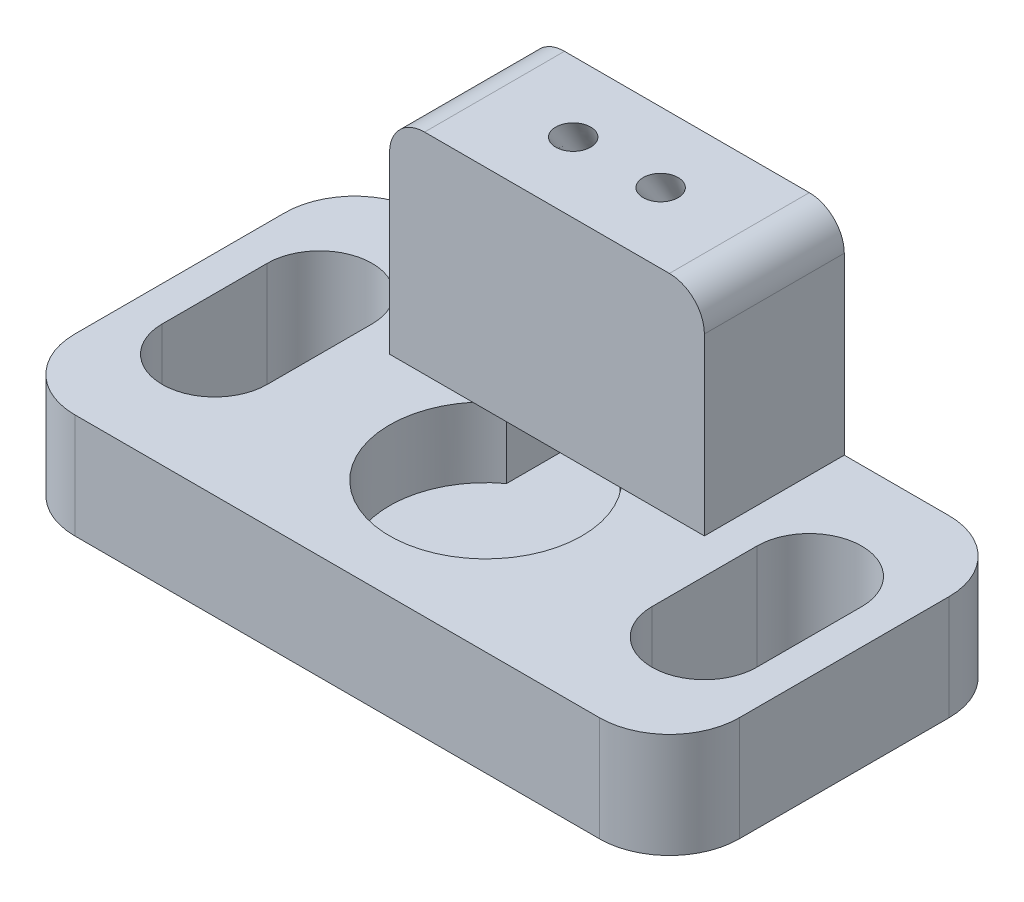
SolidWorks part; units mm, degrees
ref_plane "Front Plane" through (0, 0, 0) normal (0, 0, 1) x (1, 0, 0)
ref_plane "Top Plane" through (0, 0, 0) normal (0, 1, 0) x (1, 0, 0)
ref_plane "Right Plane" through (0, 0, 0) normal (1, 0, 0) x (0, 0, -1)
sketch "Sketch1" plane through (0, 0, 0) normal (0, 0, 1) x (1, 0, 0)
  line L1 (-4.5, -4.5) -> (4.5, -4.5)
  line L2 (-4.5, -4.5) -> (-4.5, 4.5)
  line L3 (-4.5, 4.5) -> (4.5, 4.5)
  line L4 (4.5, -4.5) -> (4.5, 4.5)
  line L5 (-4.5, -4.5) -> (4.5, 4.5) construction
  line L6 (-4.5, 4.5) -> (4.5, -4.5) construction
  point P0 (0, 0)
  dimension "D1" = 9
  dimension "D2" = 9
extrude "Boss-Extrude1" add sketch "Sketch1" along normal blind 8
sketch "Sketch3" plane through (0, 0, 0) normal (0, 0, -1) x (-1, 0, 0)
  line L1 (4.5, 4.5) -> (-4.5, 4.5)
  line L2 (4.5, 4.5) -> (4.5, -4.5)
  line L3 (4.5, -4.5) -> (-4.5, -4.5)
  line L4 (-4.5, 4.5) -> (-4.5, -4.5)
extrude "Boss-Extrude2" add sketch "Sketch3" along normal blind 2
sketch "Sketch5" plane through (0, -4.5, 0) normal (0, -1, 0) x (1, 0, 0)
  line L0 (4.5, -2) -> (-4.5, -2) construction
  line L1 (4.5, 8) -> (9.5, 8)
  line L2 (4.5, 8) -> (4.5, -2)
  line L3 (4.5, -2) -> (9.5, -2)
  line L4 (9.5, 8) -> (9.5, -2)
  line L5 (7, 4.5) -> (7, 1.5) construction
  line L6 (8.5, 4.5) -> (8.5, 1.5)
  line L7 (5.5, 4.5) -> (5.5, 1.5)
  line L8 (4.5, 3) -> (9.5, 3) construction
  line L11 (7, -2) -> (7, 8) construction
  arc A0 (8.5, 4.5) -> (5.5, 4.5) centre (7, 4.5) ccw
  arc A1 (5.5, 1.5) -> (8.5, 1.5) centre (7, 1.5) ccw
  point P9 (7, 3)
  dimension "D1" = 5
  dimension "D2" = 3
  dimension "D3" = 3
extrude "Boss-Extrude3" add sketch "Sketch5" against normal blind 3
fillet "Fillet1" radius 2 2 edges at (9.5, -3, -2) (9.5, -3, 8)
mirror "Mirror2" about plane through (0, 0, 0) normal (1, 0, 0) of "Fillet1", "Boss-Extrude3"
fillet "Fillet2" radius 1 2 edges at (4.5, 4.5, 3) (-4.5, 4.5, 3)
sketch "Sketch6" plane through (0, 0, -2) normal (0, 0, -1) x (-1, 0, 0)
  line L1 (-1.625, -3.5) -> (1.625, -3.5)
  line L2 (-1.625, -3.5) -> (-1.625, -1.5)
  line L3 (-1.625, -1.5) -> (1.625, -1.5)
  line L4 (1.625, -3.5) -> (1.625, -1.5)
  line L5 (-1.625, -3.5) -> (1.625, -1.5) construction
  line L6 (-1.625, -1.5) -> (1.625, -3.5) construction
  line L7 (-4.5, -1.5) -> (-7.5, -1.5) construction
  point P0 (0, -2.5)
  dimension "D1" = 3.25
  dimension "D2" = 2
extrude "Cut-Extrude1" cut sketch "Sketch6" against normal blind 5.75
sketch "Sketch7" plane through (4.5, 0, 0) normal (1, 0, 0) x (0, 0, -1)
  line L0 (-8, 4.5) -> (2, 4.5) construction
  line L1 (-8, -1.5) -> (-2, -1.5)
  line L2 (-8, -1.5) -> (-8, 4.5)
  line L3 (-8, 4.5) -> (-2, 4.5)
  line L4 (-2, -1.5) -> (-2, 4.5)
  line L5 (2, 3.5) -> (2, -1.5) construction
  dimension "D1" = 4
extrude "Cut-Extrude2" cut sketch "Sketch7" against normal through all
sketch "Sketch8" plane through (0, -1.5, 0) normal (0, 1, 0) x (1, 0, 0)
  line L0 (-1.625, -3.75) -> (1.625, -3.75) construction
  circle A0 centre (0, -3.75) radius 2.75
  dimension "D1" = 5.5
extrude "Cut-Extrude3" cut sketch "Sketch8" against normal up to surface (2 mm away) up to face at (0, -3.5, 0.875)
sketch "Sketch9" plane through (0, 4.5, 0) normal (0, 1, 0) x (1, 0, 0)
  line L0 (0, 2) -> (0, -2) construction
  line L1 (-3.5, 2) -> (3.5, 2) construction
  line L2 (-3.5, -2) -> (3.5, -2) construction
  circle A0 centre (-1.25, 0) radius 0.5
  circle A1 centre (1.25, 0) radius 0.5
  dimension "D2" = 1
  dimension "D1" = 2.5
sketch "Sketch10" plane through (0, 0, -2) normal (0, 0, -1) x (-1, 0, 0)
  line L0 (0, 0) -> (0, 4.5) construction
  line L1 (3.5, 4.5) -> (-3.5, 4.5) construction
  circle A0 centre (-1.25, 1) radius 0.5
  circle A1 centre (1.25, 1) radius 0.5
  dimension "D1" = 2.5
  dimension "D2" = 1
  dimension "D3" = 1
loft "Cut-Loft1" cut section "Sketch9" section "Sketch10" connector at (1.6183, 4.5, 0.3381) connector at (1.2434, 1.5, -2)
loft "Cut-Loft2" cut section "Sketch9<3>" section "Sketch10<3>" connector at (-0.7792, 4.5, -0.1685) connector at (-1.1986, 1.4973, -2)
sketch "Sketch9<3>" plane through (0, 4.5, 0) normal (0, 1, 0) x (1, 0, 0) same geometry as "Sketch9"
sketch "Sketch10<3>" plane through (0, 0, -2) normal (0, 0, -1) x (-1, 0, 0) same geometry as "Sketch10"
